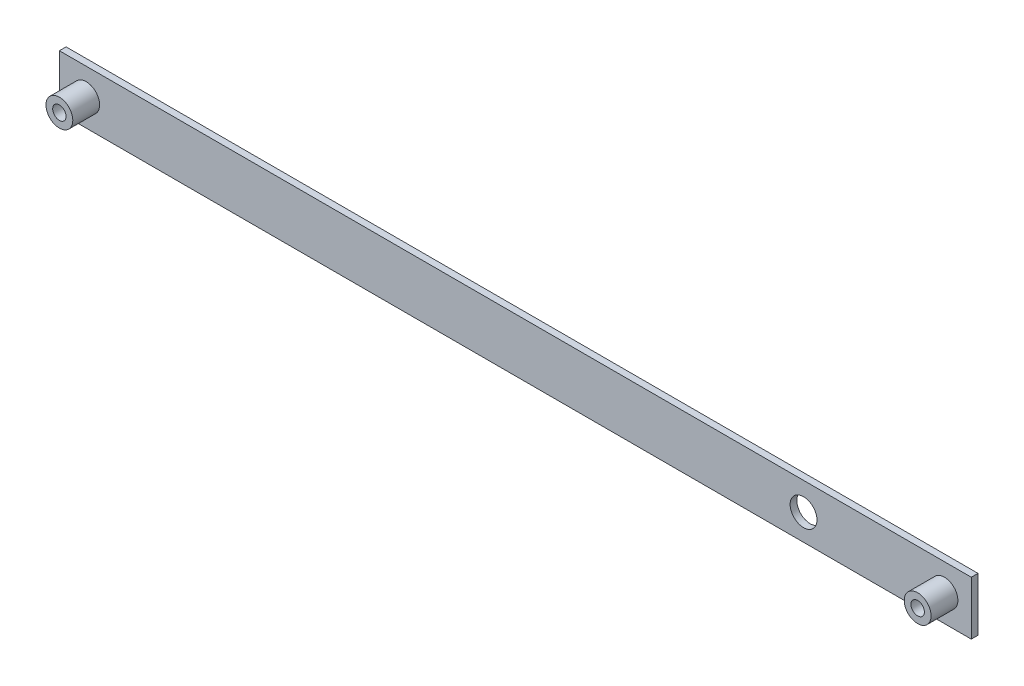
SolidWorks part; units mm, degrees
ref_plane "Front" through (0, 0, 0) normal (0, 0, 1) x (1, 0, 0)
ref_plane "Top" through (0, 0, 0) normal (0, 1, 0) x (1, 0, 0)
ref_plane "Right" through (0, 0, 0) normal (1, 0, 0) x (0, 0, -1)
sketch "Sketch1" plane through (0, 0, 0) normal (0, 0, 1) x (1, 0, 0)
  line L0 (0, 0) -> (406.4, 0) construction
  line L1 (0, 0) -> (-12.7, 0) construction
  line L2 (-12.7, 12.7) -> (419.1, 12.7)
  line L3 (-12.7, 12.7) -> (-12.7, -12.7)
  line L4 (-12.7, -12.7) -> (419.1, -12.7)
  line L5 (419.1, 12.7) -> (419.1, -12.7)
  line L6 (-12.7, 12.7) -> (419.1, -12.7) construction
  line L7 (-12.7, -12.7) -> (419.1, 12.7) construction
  line L8 (406.4, 0) -> (419.1, 0) construction
  circle A0 centre (0, 0) radius 3.175
  circle A1 centre (406.4, 0) radius 3.175
  point P5 (203.2, 0)
  dimension "D1" = 6.35
  dimension "D2" = 6.35
  dimension "D3" = 12.7
  dimension "D4" = 25.4
  dimension "D5" = 406.4
extrude "Boss-Extrude1" add sketch "Sketch1" along normal blind 3.175
sketch "Sketch2" plane through (0, 0, 3.175) normal (0, 0, 1) x (1, 0, 0)
  line L0 (406.4, 0) -> (0, 0) construction
  circle A1 centre (0, 0) radius 3.175
  circle A2 centre (0, 0) radius 6.35
  circle A3 centre (406.4, 0) radius 3.175 construction
  circle A4 centre (406.4, 0) radius 3.175
  circle A5 centre (406.4, 0) radius 6.35
  point P0 (32.1946, 0)
  point P4 (0, 0)
  dimension "D1" = 12.7
  dimension "D2" = 12.7
  dimension "D3" = 406.4
extrude "Boss-Extrude2" add sketch "Sketch2" along normal blind 12.7
sketch "Sketch3" plane through (0, 0, 3.175) normal (0, 0, 1) x (1, 0, 0)
  circle A1 centre (339.6683, -0.34) radius 6.35
extrude "Cut-Extrude1" cut sketch "Sketch3" against normal up to next
